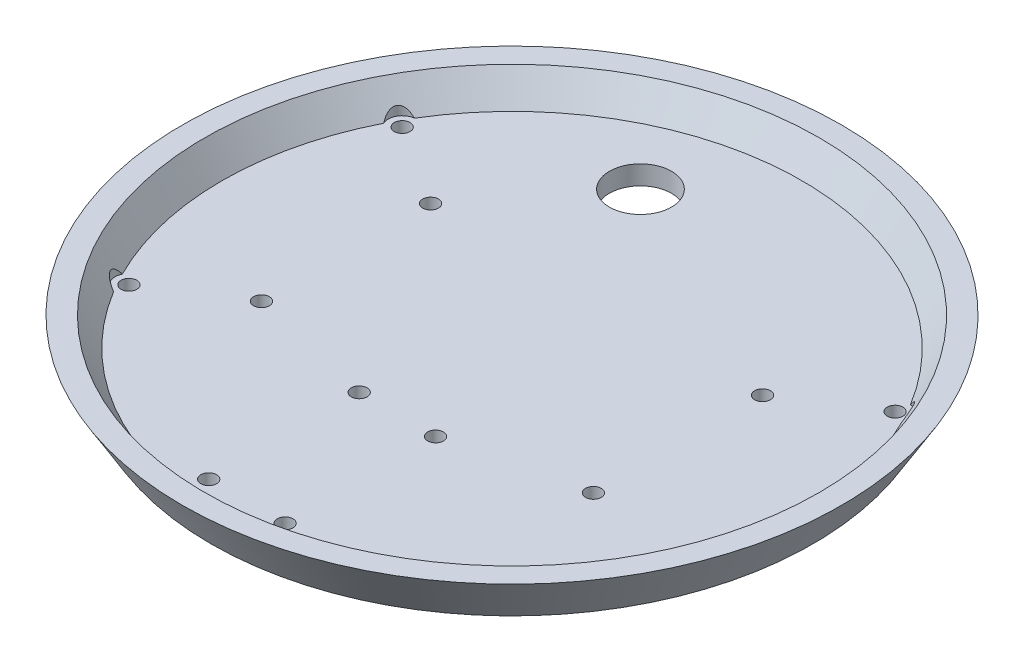
SolidWorks part; units mm, degrees
ref_plane "Front Plane" through (0, 0, 0) normal (0, 0, 1) x (1, 0, 0)
ref_plane "Top Plane" through (0, 0, 0) normal (0, 1, 0) x (1, 0, 0)
ref_plane "Right Plane" through (0, 0, 0) normal (1, 0, 0) x (0, 0, -1)
sketch "Sketch1" plane through (0, 0, 0) normal (0, 0, 1) x (1, 0, 0)
  line L0 (0, -4) -> (63, -4)
  line L1 (63, -4) -> (69, 6)
  line L6 (0, 0) -> (60.7352, 0)
  line L7 (60.7352, 0) -> (64.3352, 6)
  line L8 (69, 6) -> (64.3352, 6)
  line L9 (0, -4) -> (0, 0)
  line L10 (60.7352, 0) -> (65.57, 8.058) construction
  dimension "D1" = 69
  dimension "D2" = 63
  dimension "D3" = 10
  dimension "D4" = 4
revolve "Revolve1" add sketch "Sketch1" angle 360 about L9
sketch "Sketch4" plane through (0, 0, 0) normal (0, 1, 0) x (1, 0, 0)
  line L0 (-60.7352, 0) -> (60.7352, 0) construction
  line L1 (0, 60.7352) -> (0, -60.7352) construction
  line L2 (0, 0) -> (34.7493, 17.7056) construction
  line L3 (0, 0) -> (51.6026, 28.6038) construction
  circle A0 centre (0, 0) radius 60.7352 construction
  circle A1 centre (34.7493, 17.7056) radius 1.65
  circle A2 centre (51.6026, 28.6038) radius 1.65
  circle A4 centre (51.6026, -28.6038) radius 1.65
  circle A5 centre (34.7493, -17.7056) radius 1.65
  circle A6 centre (-34.7493, -17.7056) radius 1.65
  circle A7 centre (-51.6026, -28.6038) radius 1.65
  circle A8 centre (-51.6026, 28.6038) radius 1.65
  circle A9 centre (-34.7493, 17.7056) radius 1.65
  dimension "D5" = 3.3
  dimension "D6" = 3.3
  dimension "D1" = 27
  dimension "D2" = 29
  dimension "D3" = 39
  dimension "D4" = 59
extrude "Cut-Extrude1" cut sketch "Sketch4" against normal through all
sketch "Sketch5" plane through (0, 0, 0) normal (0, 1, 0) x (1, 0, 0)
  circle A0 centre (51.6026, 28.6038) radius 2.9
  circle A1 centre (51.6026, -28.6038) radius 2.9
  circle A2 centre (-51.6026, -28.6038) radius 2.9
  circle A3 centre (-51.6026, 28.6038) radius 2.9
  dimension "D1" = 5.8
extrude "Cut-Extrude2" cut sketch "Sketch5" along normal through all
sketch "Sketch6" plane through (0, 0, 0) normal (0, 1, 0) x (1, 0, 0)
  line L0 (8, -55.5) -> (-8, -55.5) construction
  circle A0 centre (8, -55.5) radius 1.65
  circle A1 centre (-8, -55.5) radius 1.65
  circle A2 centre (8, -24) radius 1.65
  circle A3 centre (-8, -24) radius 1.65
  point P8 (0, -55.5)
  dimension "D1" = 16
  dimension "D2" = 3.3
  dimension "D3" = 31.5
  dimension "D4" = 55.5
extrude "Cut-Extrude3" cut sketch "Sketch6" against normal through all
sketch "Sketch7" plane through (0, 0, 0) normal (0, 1, 0) x (1, 0, 0)
  line L0 (0, 0) -> (-15.3909, 42.2862) construction
  line L1 (0, 0) -> (0, 50000) construction
  circle A0 centre (-15.3909, 42.2862) radius 6.5
  dimension "D1" = 13
  dimension "D2" = 20
  dimension "D3" = 45
extrude "Cut-Extrude4" cut sketch "Sketch7" against normal blind 10
